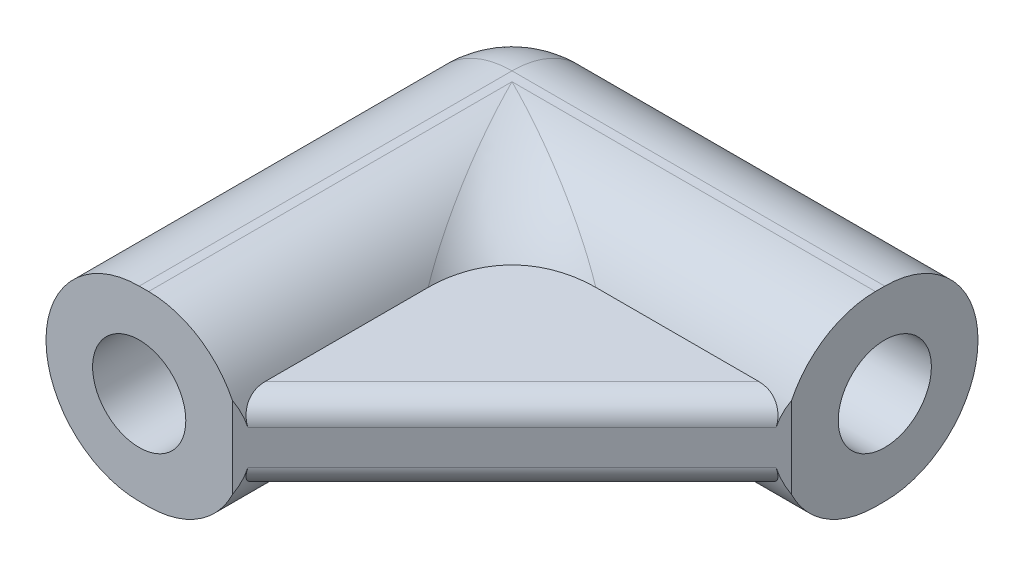
SolidWorks part; units mm, degrees
material "ABS"
ref_plane "Front Plane" through (0, 0, 0) normal (0, 0, 1) x (1, 0, 0)
ref_plane "Top Plane" through (0, 0, 0) normal (0, 1, 0) x (1, 0, 0)
ref_plane "Right Plane" through (0, 0, 0) normal (1, 0, 0) x (0, 0, -1)
sketch "Sketch1" plane through (0, 0, 0) normal (0, 1, 0) x (1, 0, 0)
  line L1 (0, -24) -> (-16, -24)
  line L2 (24, 0) -> (24, 16)
  line L3 (24, 16) -> (-16, 16)
  line L4 (-16, -24) -> (-16, 16)
  line L8 (0, -24) -> (0, 0)
  line L9 (0, 0) -> (24, 0)
  point P0 (0, 0)
  dimension "D1" = 16
  dimension "D2" = 16
  dimension "D3" = 40
  dimension "D4" = 40
extrude "Boss-Extrude1" add sketch "Sketch1" along normal blind 16
sketch "Sketch2" plane through (0, 0, 24) normal (0, 0, 1) x (1, 0, 0)
  line L0 (0, 16) -> (0, 0) construction
  line L1 (-16, 0) -> (0, 0) construction
  circle A0 centre (-8, 8) radius 4
  point P7 (-8, 0)
  dimension "D1" = 8
  dimension "D2" = 8
  dimension "D3" = 8
sketch "Sketch3" plane through (24, 0, 0) normal (1, 0, 0) x (0, 0, -1)
  line L0 (0, 16) -> (16, 16) construction
  line L1 (0, 16) -> (0, 0) construction
  circle A0 centre (8, 8) radius 4
  dimension "D1" = 8
  dimension "D2" = 8
  dimension "D3" = 8
extrude "Cut-Extrude1" cut sketch "Sketch3" against normal blind 24
extrude "Cut-Extrude2" cut sketch "Sketch2" against normal blind 24
ref_plane "Plane1" through (0, 8, 0) normal (0, 1, 0) x (1, 0, 0)
sketch "Sketch6" plane through (0, 8, 0) normal (0, 1, 0) x (1, 0, 0)
  line L0 (0, -24) -> (24, 0)
rib "Rib6" sketch "Sketch6" sketch "Sketch6" thickness 7 extrusion direction parallel to sketch draft on no parameters "D1"=7
fillet "Fillet1" radius 8 4 edges at (12, 16, 0) (0, 16, 12) (4, 16, -16) (-16, 16, 4)
fillet "Fillet4" radius 8 2 edges at (-13.6569, 13.6569, -13.6569) (-16, 4, -16)
fillet "Fillet5" radius 8 2 edges at (0, 2.25, 0) (-2.9511, 14.7823, -2.9511)
fillet "Fillet6" radius 8 6 edges at (-13.6569, 0, -13.6569) (-16, 0, 8) (8, 0, -16) (16, 0, 0) (0, 0, 16) (2.3431, 0, 2.3431)
fillet "Fillet7" radius 2 2 edges at (12, 4.5, 12) (12, 11.5, 12)
